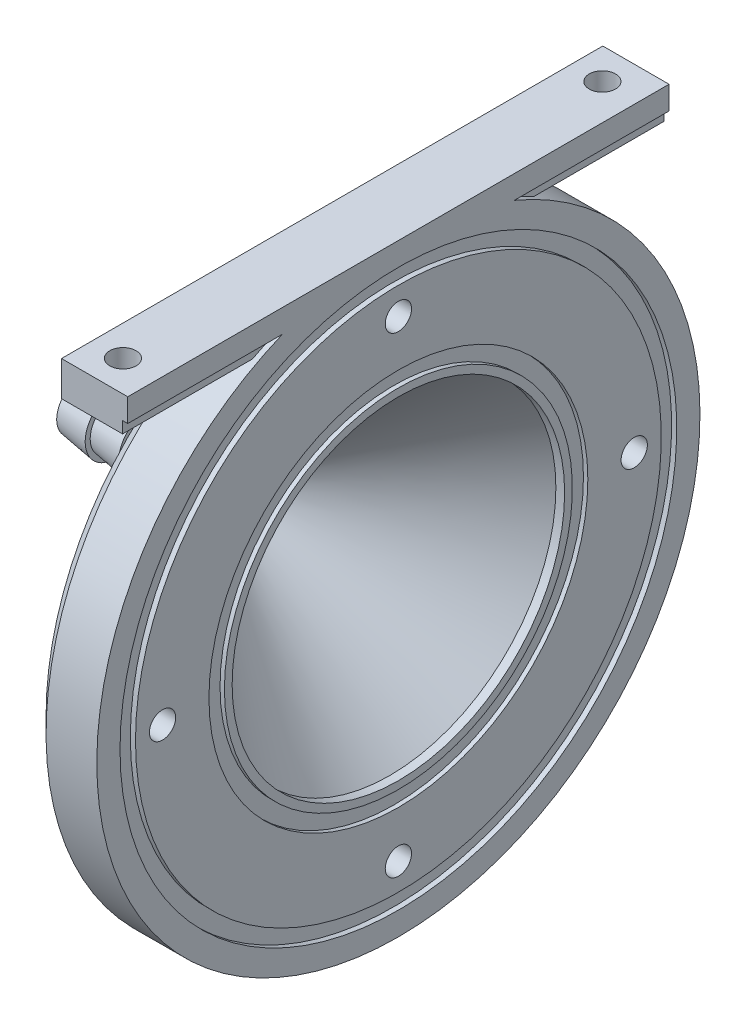
SolidWorks part; units mm, degrees
note: The reader was unsure of these and kept them because the rebuilt part matched: shared geometry of "Sketch1<11>".
ref_plane "Front Plane" through (0, 0, 0) normal (0, 0, 1) x (1, 0, 0)
ref_plane "Top Plane" through (0, 0, 0) normal (0, 1, 0) x (1, 0, 0)
ref_plane "Right Plane" through (0, 0, 0) normal (1, 0, 0) x (0, 0, -1)
sketch "Sketch1" plane through (0, 0, 0) normal (0, 0, 1) x (1, 0, 0)
  line L0 (-801.9271, 0) -> (36107.5217, 0) construction
  line L3 (-14.0102, 3.8) -> (-14.0102, 3.15)
  line L8 (-18.3435, 1.9) -> (0, 1.9)
  line L9 (-18.3435, 1.9) -> (-18.3435, 3.15)
  line L10 (22.6971, 24.5) -> (22.6971, 39)
  line L12 (22.6971, 39) -> (14.1311, 39)
  line L16 (22.6971, 24.5) -> (22.1311, 24.5)
  line L17 (22.1311, 24.5) -> (22.1311, 21.5)
  line L18 (14.1311, 39) -> (14.1311, 21.5)
  line L20 (0, 1.9) -> (21.5651, 21.5)
  line L21 (-18.3435, 3.15) -> (-14.0102, 3.8)
  line L22 (21.5651, 21.5) -> (22.1311, 21.5)
  line L23 (-14.0102, 3.15) -> (-9.6768, 3.8)
  line L25 (-9.6768, 3.15) -> (-5.3435, 3.8)
  line L26 (-9.6768, 3.8) -> (-9.6768, 3.15)
  line L27 (-5.3435, 3.8) -> (14.1311, 21.5)
  line L28 (14.1311, 34.5) -> (22.6971, 34.5)
  line L32 (22.1311, 22.5) -> (22.6971, 22.5)
  line L33 (22.6971, 22.5) -> (22.6971, 21.5)
  line L35 (22.6971, 21.5) -> (22.1311, 21.5)
  line L36 (14.1311, 39) -> (22.6971, 39)
  line L38 (22.6971, 36) -> (22.0301, 36)
  line L39 (22.0301, 36) -> (22.0301, 34)
  line L40 (22.0301, 34) -> (22.6971, 34)
  dimension "D3" = 0.566
  dimension "D2" = 7.6
  dimension "D6" = 3.8
  dimension "D7" = 6.3
  dimension "D5" = 39
  dimension "D8" = 24.5
  dimension "D4" = 5
  dimension "D9" = 0.566
  dimension "D11" = 13
  dimension "D12" = 8.566
  dimension "D13" = 4.5
  dimension "D17" = 36
  dimension "D18" = 2
  dimension "D19" = 0.667
  dimension "D14" = 1
  dimension "D10" = 2
revolve "Revolve17" add sketch "Sketch1" angle 360 about L0
sketch "Sketch4" plane through (14.1311, 0, 0) normal (-1, 0, 0) x (0, 0, 1)
  circle A0 centre (0, 0) radius 30.5 construction
  circle A2 centre (0, 0) radius 39 construction
  point P3 (0, 30.5)
  point P7 (30.5, 0)
  point P12 (-30.5, 0)
  point P13 (0, -30.5)
  dimension "D1" = 8.5
hole_wizard "M3 Clearance Hole1" positions "Sketch4" profile "Sketch5" hole size "M3" standard "ISO"
sketch "Sketch5" plane through (14.1311, -30.5, 0) normal (0, 1, 0) x (0, 0, 1)
  line L0 (0, 0) -> (0, 9.5875)
  line L1 (0, 9.5875) -> (1.7, 8.566)
  line L2 (1.7, 8.566) -> (1.7, 0)
  line L5 (1.7, 0) -> (0, 0)
  line L10 (0, 9.5875) -> (-1.7, 8.566) construction
  line L11 (0, -6.35) -> (0, 107.95) construction
  dimension "Hole Dia." = 3.4
  dimension "Hole Depth" = 8.566
  dimension "Drill Angle" = 118
chamfer "Chamfer1" distance 2 angle 45 1 edges at (14.1311, 0, 39)
extrude "Boss-Extrude1" add sketch "Sketch1<11>" against normal mid plane 70 contours L18 L28 L10 L12
sketch "Sketch1<11>" plane through (0, 0, 0) normal (0, 0, 1) x (1, 0, 0) same geometry as "Sketch1"
sketch "Sketch9" plane through (0, 34.5, 0) normal (0, -1, 0) x (-1, 0, 0)
  line L0 (-14.1311, -35) -> (-22.6971, 35) construction
  line L1 (-14.1311, -13.3697) -> (-14.1311, -35) construction
  line L2 (-14.1311, -35) -> (-22.0301, -35) construction
  line L3 (-22.6971, 35) -> (-22.6971, -18.1865) construction
  line L4 (-22.6971, 35) -> (-13.4641, 35) construction
  line L5 (-14.1311, 35) -> (-22.0301, 35) construction
  line L6 (-13.4641, 35) -> (-22.6971, -35) construction
  line L7 (-22.6971, -18.1865) -> (-22.6971, -35) construction
  line L8 (-18.0806, -35) -> (-18.0806, 35) construction
  line L9 (-4.5963, 0) -> (-22.6971, 0) construction
  line L10 (-22.6971, 39) -> (-22.6971, -39) construction
  circle A0 centre (-18.0806, -31) radius 1.7
  circle A1 centre (-18.0806, 31) radius 1.7
  dimension "D1" = 3.4
  dimension "D2" = 4
extrude "Cut-Extrude1" cut sketch "Sketch9" against normal blind 10
sketch "Sketch10" plane through (14.1311, 0, 0) normal (-1, 0, 0) x (0, 0, 1)
  line L0 (37, 0) -> (21.5, 0)
  line L1 (-21.5, 0) -> (-37, 0)
  line L2 (0, -21.5) -> (0, -37)
  circle A1 centre (0, 0) radius 21.5 construction
  point P15 (0, 30.467)
equation "\"D9@Sketch1\"=\"D3@Sketch1\""
